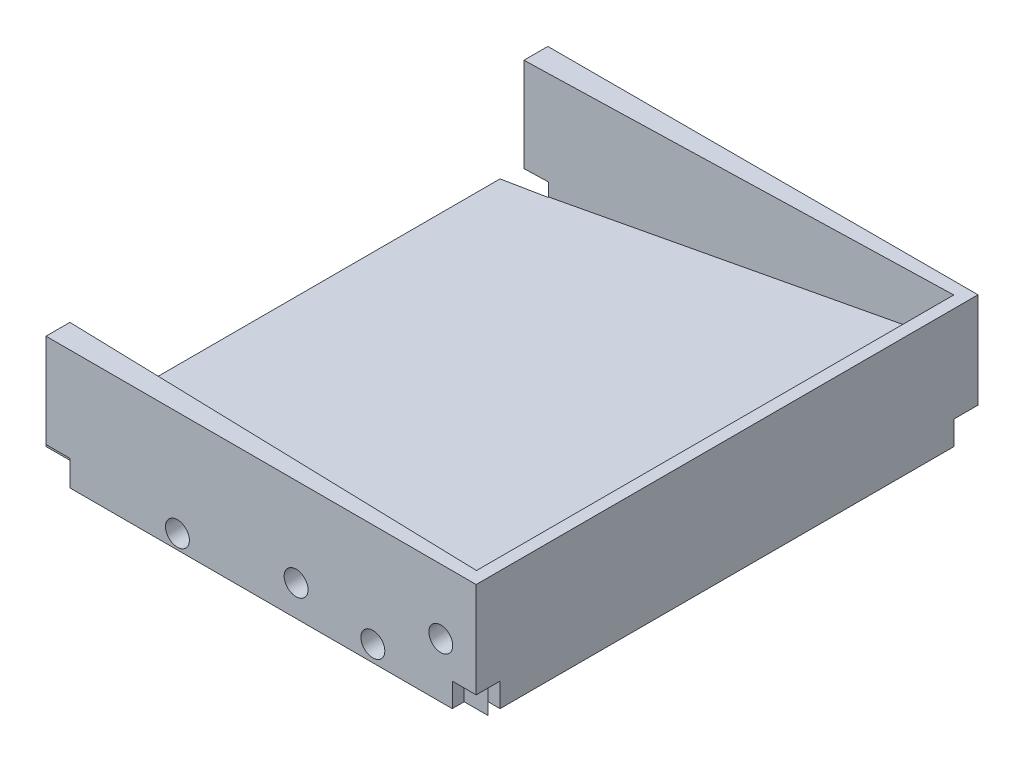
SolidWorks part; units mm, degrees
ref_plane "Plan de face" through (0, 0, 0) normal (0, 0, 1) x (1, 0, 0)
ref_plane "Plan de dessus" through (0, 0, 0) normal (0, 1, 0) x (1, 0, 0)
ref_plane "Plan de droite" through (0, 0, 0) normal (1, 0, 0) x (0, 0, -1)
sketch "Esquisse1" plane through (0, 0, 0) normal (0, 0, 1) x (1, 0, 0)
  line L0 (-105.796, 0) -> (84.204, 0)
  line L1 (84.204, 0) -> (84.204, 33.5021)
  line L2 (84.204, 25.3929) -> (-68.9493, 0) construction
  line L3 (-105.796, 0) -> (-105.796, 2)
  line L4 (-105.796, 2) -> (84.204, 33.5021)
  line L5 (40.9815, 6.7762) -> (8.8615, 12.9011) construction
  line L6 (69.406, 22.9394) -> (40.9815, 6.7762) construction
  circle A0 centre (69.406, 22.9394) radius 3
  circle A1 centre (40.9815, 6.7762) radius 3
  circle A2 centre (-40.796, 6) radius 3
  circle A3 centre (8.8615, 12.9011) radius 3
  dimension "D3" = 6
  dimension "D6" = 6
  dimension "D8" = 6
  dimension "D11" = 6
  dimension "D1" = 190
  dimension "D2" = 2
  dimension "D4" = 15
  dimension "D7" = 8
  dimension "D9" = 6
  dimension "D10" = 65
extrude "Boss.-Extru.1" add sketch "Esquisse1" along normal blind 200
sketch "Esquisse4" plane through (84.204, 0, 0) normal (1, 0, 0) x (0, 0, -1)
  line L1 (-200, 0) -> (-205, 0)
  line L2 (-200, 0) -> (-200, 50)
  line L3 (-200, 50) -> (-205, 50)
  line L4 (-205, 0) -> (-205, 50)
  line L5 (0, 0) -> (5, 0)
  line L6 (0, 0) -> (0, 50)
  line L7 (0, 50) -> (5, 50)
  line L8 (5, 0) -> (5, 50)
  dimension "D1" = 50
  dimension "D2" = 5
  dimension "D3" = 5
  dimension "D4" = 50
extrude "Boss.-Extru.4" add sketch "Esquisse4" against normal blind 180
sketch "Esquisse8" plane through (0, 50, 0) normal (0, 1, 0) x (1, 0, 0)
  line L0 (84.204, 0) -> (-95.796, 0)
  line L1 (-95.796, 0) -> (-95.796, -5)
  line L2 (-95.796, -5) -> (84.204, 0)
  dimension "D1" = 5
extrude "Boss.-Extru.7" add sketch "Esquisse8" against normal up to surface (50 mm away) up to face at (-54.546, 0, 100.625)
ref_plane "Plan2" through (-5.796, 0, 0) normal (1, 0, 0) x (0, 0, -1)
sketch "Esquisse6" plane through (0, 0, -5) normal (0, 0, -1) x (-1, 0, 0)
  line L1 (105.796, 0) -> (85.796, 0)
  line L2 (105.796, 0) -> (105.796, 10.7198)
  line L3 (105.796, 10.7198) -> (85.796, 10.7198)
  line L4 (85.796, 0) -> (85.796, 10.7198)
  line L5 (95.796, 0) -> (95.796, 50) construction
  dimension "D1" = 10
extrude "Enlèv. mat.-Extru.2" cut sketch "Esquisse6" against normal blind 10
ref_plane "Plan3" through (0, 0, 100) normal (0, 0, -1) x (-1, 0, 0)
sketch "Esquisse5" plane through (84.204, 0, 0) normal (1, 0, 0) x (0, 0, -1)
  line L1 (-205, 0) -> (-195, 0)
  line L2 (-205, 0) -> (-205, 10)
  line L3 (-205, 10) -> (-195, 10)
  line L4 (-195, 0) -> (-195, 10)
  line L5 (5, 0) -> (-5, 0)
  line L6 (5, 0) -> (5, 10)
  line L7 (5, 10) -> (-5, 10)
  line L8 (-5, 0) -> (-5, 10)
  dimension "D1" = 10
  dimension "D2" = 10
  dimension "D3" = 10
  dimension "D4" = 10
extrude "Enlèv. mat.-Extru.1" cut sketch "Esquisse5" against normal blind 10
sketch "Esquisse14" plane through (0, 0, -5) normal (0, 0, -1) x (-1, 0, 0)
  circle A0 centre (-69.406, 22.9394) radius 5
  circle A1 centre (-40.9815, 6.7762) radius 5
  circle A2 centre (-8.8615, 12.9011) radius 5
  circle A3 centre (40.796, 6) radius 5
  dimension "D1" = 10
  dimension "D2" = 10
  dimension "D3" = 10
  dimension "D4" = 10
extrude "Enlèv. mat.-Extru.4" cut sketch "Esquisse14" against normal blind 15
mirror "Symétrie3" about plane through (0, 0, 100) normal (0, 0, -1) of "Enlèv. mat.-Extru.4", "Boss.-Extru.7", "Enlèv. mat.-Extru.2"
sketch "Esquisse15" plane through (0, 0, -5) normal (0, 0, -1) x (-1, 0, 0)
  line L0 (-84.204, 33.5021) -> (-79.204, 32.6731)
  line L1 (-84.204, 33.5021) -> (85.796, 5.316) construction
  line L2 (-79.204, 32.6731) -> (-79.204, 50)
  line L3 (95.796, 50) -> (-84.204, 50) construction
  line L4 (-79.204, 50) -> (-84.204, 50)
  line L5 (-84.204, 50) -> (-84.204, 33.5021)
  dimension "D1" = 5
extrude "Boss.-Extru.8" add sketch "Esquisse15" against normal up to surface (204.8611 mm away) up to face at (-18.296, 27.6837, 197.1528)
